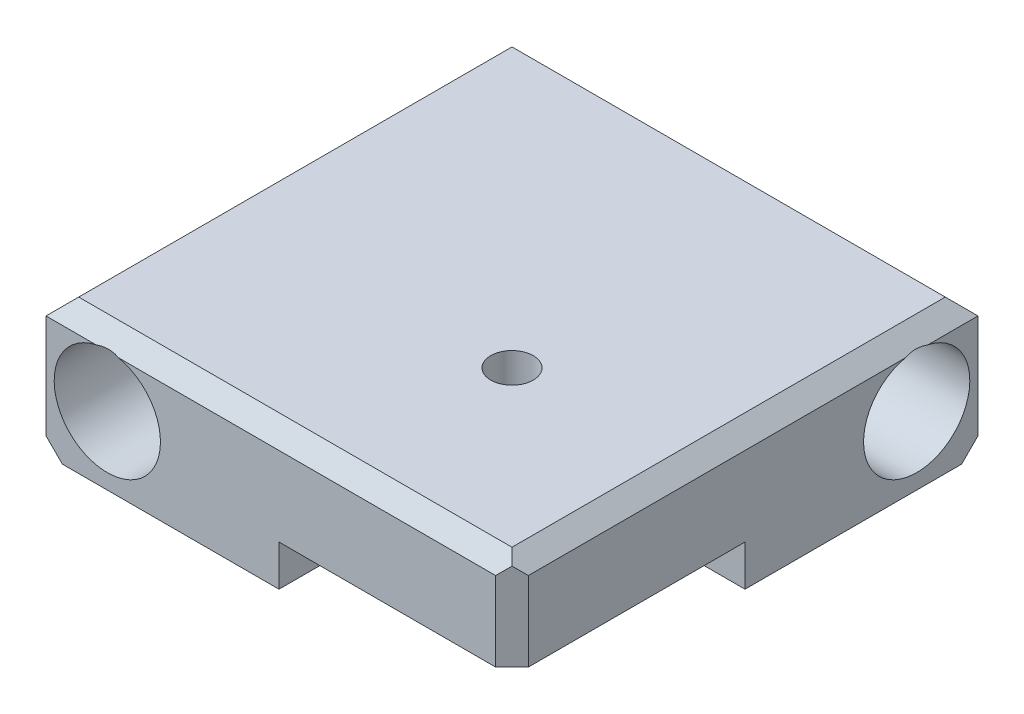
SolidWorks part; units mm, degrees
ref_plane "Front Plane" through (0, 0, 0) normal (0, 0, 1) x (1, 0, 0)
ref_plane "Top Plane" through (0, 0, 0) normal (0, 1, 0) x (1, 0, 0)
ref_plane "Right Plane" through (0, 0, 0) normal (1, 0, 0) x (0, 0, -1)
sketch "Sketch1" plane through (0, 0, 0) normal (0, 1, 0) x (1, 0, 0)
  line L1 (7.5, -5) -> (-7.5, -5)
  line L2 (7.5, -5) -> (7.5, 5)
  line L3 (7.5, 5) -> (-7.5, 5)
  line L4 (-7.5, -5) -> (-7.5, 5)
  line L5 (7.5, -5) -> (-7.5, 5) construction
  line L6 (7.5, 5) -> (-7.5, -5) construction
  line L8 (-7.5, 5) -> (-7.5, 20)
  line L9 (-7.5, 20) -> (7.5, 20)
  line L10 (7.5, 5) -> (7.5, 20)
  line L11 (7.5, 5) -> (17.5, 5)
  line L13 (7.5, 20) -> (17.5, 20)
  line L14 (17.5, 5) -> (17.5, 20)
  point P0 (0, 0)
  dimension "D1" = 10
  dimension "D2" = 15
  dimension "D3" = 15
  dimension "D4" = 10
extrude "Boss-Extrude1" add sketch "Sketch1" along normal blind 16.7 contours L4 L1 L2 L3 | L3 L10 L9 L8 | L11 L14 L13 L10 region at (0, 0, 0) region at (0, 0, -12.5) region at (12.5, 0, -12.5)
sketch "Sketch2" plane through (0, 0, 5) normal (0, 0, 1) x (1, 0, 0)
  line L0 (0, 0) -> (0, 16.7) construction
  line L1 (7.5, 0) -> (-7.5, 0) construction
  line L2 (7.5, 16.7) -> (-7.5, 16.7) construction
  circle A0 centre (0, 8.35) radius 6.5
  dimension "D1" = 13
extrude "Cut-Extrude1" cut sketch "Sketch2" against normal offset from surface (8.3 mm away) 16.7 up to face at (5, 8.35, -20)
sketch "Sketch3" plane through (17.5, 0, 0) normal (1, 0, 0) x (0, 0, -1)
  line L0 (12.5, 0) -> (12.5, 16.7) construction
  line L1 (5, 0) -> (20, 0) construction
  line L2 (5, 16.7) -> (20, 16.7) construction
  circle A0 centre (12.5, 8.35) radius 6.5
  dimension "D1" = 13
extrude "Cut-Extrude2" cut sketch "Sketch3" against normal offset from surface (8.3 mm away) 16.7 up to face at (-7.5, 8.35, -7.5)
sketch "Sketch4" plane through (0, 0, 0) normal (0, -1, 0) x (1, 0, 0)
  line L0 (0, 5) -> (0, -20) construction
  line L1 (7.5, 5) -> (-7.5, 5) construction
  line L2 (-7.5, -20) -> (17.5, -20) construction
  line L3 (17.5, -12.5) -> (-7.5, -12.5) construction
  line L4 (17.5, -5) -> (17.5, -20) construction
  line L5 (-7.5, 5) -> (-7.5, -20) construction
  circle A0 centre (0, -12.5) radius 6.5
  dimension "D1" = 13
extrude "Cut-Extrude3" cut sketch "Sketch4" against normal offset from surface (14.7 mm away) 2 up to face at (5.8333, 16.7, -6.6667)
fillet "Fillet8" radius 2 5 edges at (-7.5, 8.35, -20) (-7.5, 0, -7.5) (-7.5, 16.7, -7.5) (5, 16.7, -20) (5, 0, -20) profile chamfer
sketch "Sketch5" plane through (0, 16.7, 0) normal (0, 1, 0) x (1, 0, 0)
  line L1 (7.5, -37) -> (49.5, -37)
  line L2 (7.5, -37) -> (7.5, 5)
  line L3 (7.5, 5) -> (49.5, 5)
  line L4 (49.5, -37) -> (49.5, 5)
  line L6 (7.5, -16) -> (49.5, -16) construction
  line L7 (28.5, 5) -> (28.5, -37) construction
  line L8 (29.5, -17) -> (27.5, -17)
  line L9 (29.5, -17) -> (29.5, -15)
  circle A4 centre (28.5, -16) radius 2.6
  point P14 (28.5, 0)
  point P15 (12.5, -16)
  point P17 (28.5, -17)
  point P18 (29.5, -16)
  line M12 (7.5, -5) -> (7.5, 5)
  line M14 (7.5, 5) -> (17.5, 5)
  dimension "D8" = 5.2
  dimension "D1" = 42
  dimension "D2" = 42
extrude "Boss-Extrude3" add sketch "Sketch5" against normal up to surface (16.7 mm away) contours L1 L4 L3 L2 L9 L8 M14 M12 | L8 L9 region at (8.094, 16.7, 21) up to face at (6.8683, 0, -5.6317)
fillet "Fillet9" radius 2 1 edges at (49.5, 8.35, 37) profile chamfer
sketch "Sketch7" plane through (0, 0, 5) normal (0, 0, 1) x (1, 0, 0)
  line L0 (-5.5, 16.7) -> (-7.5, 14.7)
  line L1 (-5.5, 16.7) -> (-7.5, 14.7) construction
  line L2 (-7.5, 14.7) -> (-7.5, 2)
  line L3 (-7.5, 2) -> (-5.5, 0)
  line L4 (-5.5, 0) -> (7.5, 0)
  line L5 (7.5, 0) -> (7.5, 16.7)
  line L6 (7.5, 16.7) -> (-5.5, 16.7)
  circle A0 centre (0, 8.35) radius 6.5
extrude "Boss-Extrude4" add sketch "Sketch7" along normal up to surface (32 mm away) up to face at (27.5, 8.35, 37)
sketch "Sketch8" plane through (17.5, 0, 0) normal (1, 0, 0) x (0, 0, -1)
  line L0 (5, 16.7) -> (5, 0)
  line L1 (5, 0) -> (18, 0)
  line L2 (18, 0) -> (20, 2)
  line L3 (20, 2) -> (20, 14.7)
  line L4 (20, 14.7) -> (18, 16.7)
  line L5 (18, 16.7) -> (5, 16.7)
  circle A0 centre (12.5, 8.35) radius 6.5
extrude "Boss-Extrude5" add sketch "Sketch8" along normal up to surface (32 mm away) up to face at (49.5, 8.35, 15)
sketch "Sketch9" plane through (0, 0, 0) normal (0, -1, 0) x (1, 0, 0)
  line L0 (28.5, 8.5) -> (49.5, 8.5)
  line L1 (49.5, -18) -> (49.5, 35) construction
  line L2 (49.5, 8.5) -> (49.5, 35)
  line L3 (49.5, 35) -> (47.5, 37)
  line L4 (47.5, 37) -> (28.5, 37)
  line L5 (47.5, 37) -> (-5.5, 37) construction
  line L6 (28.5, 37) -> (21, 37)
  line L7 (21, 37) -> (21, 16)
  arc A0 (21, 16) -> (28.5, 8.5) centre (28.5, 16) ccw
  dimension "D1" = 15
extrude "Cut-Extrude4" cut sketch "Sketch9" against normal blind 5
chamfer "Chamfer1" distance 2 angle 45 2 edges at (49.5, 16.7, 8.5) (21, 16.7, 37)
